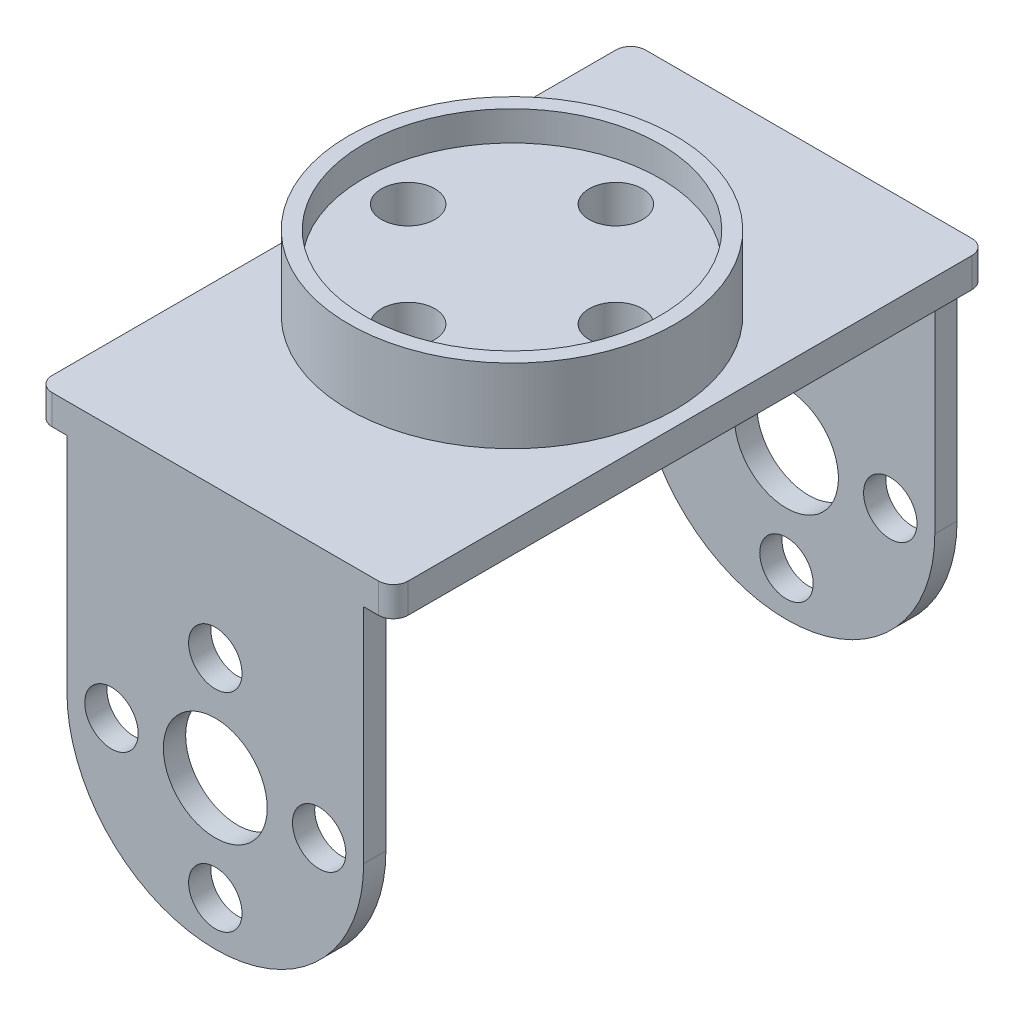
SolidWorks part; units mm, degrees
ref_plane "前视基准面" through (0, 0, 0) normal (0, 0, 1) x (1, 0, 0)
ref_plane "上视基准面" through (0, 0, 0) normal (0, 1, 0) x (1, 0, 0)
ref_plane "右视基准面" through (0, 0, 0) normal (1, 0, 0) x (0, 0, -1)
other "Configuration Table"
sketch "草图1" plane through (0, 0, 0) normal (0, 0, 1) x (1, 0, 0)
  line L1 (0, 0) -> (-24, 0)
  line L2 (0, 0) -> (0, 30)
  line L3 (0, 30) -> (-24, 30)
  line L4 (-24, 0) -> (-24, 30)
  dimension "D1" = 30
  dimension "D2" = 24
extrude "凸台-拉伸1" add sketch "草图1" along normal blind 40
sketch "草图2" plane through (0, 0, 0) normal (0, 0, -1) x (-1, 0, 0)
  line L0 (12, 0) -> (12, 50000) construction
  line L1 (24, 0) -> (0, 0) construction
  line L2 (0, 30) -> (24, 30) construction
  line L3 (2, 13) -> (2, 28)
  line L4 (2, 28) -> (0, 28)
  line L5 (0, 0) -> (0, 30) construction
  line L6 (24, 30) -> (24, 28)
  line L7 (22, 28) -> (24, 28)
  line L8 (22, 13) -> (22, 28)
  line L10 (0, 30) -> (0, 0)
  line L11 (0, 0) -> (24, 0)
  line L12 (24, 0) -> (24, 30)
  line L13 (24, 30) -> (0, 30)
  line L14 (0, 30) -> (0, 28)
  line L17 (24, 30) -> (0, 30)
  circle A0 centre (12, 13) radius 10
  point P4 (12, 0)
  line M13 (0, 30) -> (0, 0)
  line M14 (0, 0) -> (24, 0)
  line M15 (24, 0) -> (24, 30)
  dimension "D1" = 20
  dimension "D2" = 17
  dimension "D3" = 0
  dimension "D4" = 2
extrude "切除-拉伸1" cut sketch "草图2" against normal through all contours L0 A0 L3 L4 M14 M13 | L0 L7 L8 A0 M14 M15 region at (-6, 0.3046, 0) region at (-12.3046, 1.5, 0)
ref_plane "基准面1" through (0, 0, 20) normal (0, 0, -1) x (-1, 0, 0)
sketch "草图3" plane through (0, 0, 20) normal (0, 0, -1) x (-1, 0, 0)
  line L0 (2, 28) -> (22, 28)
  line L7 (0, 30) -> (0, 28)
  line L8 (0, 28) -> (2, 28)
  line L9 (2, 28) -> (2, 13)
  line L10 (22, 13) -> (22, 28)
  line L11 (22, 28) -> (24, 28)
  line L12 (24, 28) -> (24, 30)
  line L13 (24, 30) -> (0, 30)
  line L14 (0, 30) -> (0, 28)
  line L15 (0, 28) -> (2, 28)
  line L16 (2, 28) -> (2, 13)
  line L17 (22, 13) -> (22, 28)
  line L18 (22, 28) -> (24, 28)
  line L19 (24, 28) -> (24, 30)
  line L20 (24, 30) -> (0, 30)
  arc A1 (2, 13) -> (22, 13) centre (12, 13) ccw
  arc A2 (2, 13) -> (22, 13) centre (12, 13) ccw
  dimension "D1" = 0
extrude "切除-拉伸2" cut sketch "草图3" against normal blind 18.5 and the other way blind 18.5 contours L16 A2 L17 L0 region at (-12, 16.464, 20)
sketch "草图4" plane through (0, 0, 0) normal (0, 0, -1) x (-1, 0, 0)
  circle A0 centre (12, 13) radius 7 construction
  circle A1 centre (12, 6) radius 1.8
  circle A5 centre (12, 13) radius 3.5
  circle A6 centre (12, 20) radius 1.8
  circle A7 centre (19, 13) radius 1.8
  circle A8 centre (5, 13) radius 1.8
  point P14 (11.0448, 11.9373)
  dimension "D1" = 14
  dimension "D2" = 3.6
  dimension "D4" = 7
  dimension "D3" = 3.6
  dimension "D5" = 3.6
  dimension "D6" = 3.6
extrude "切除-拉伸3" cut sketch "草图4" against normal up to surface (40 mm away) up to face at (-12, 23.5, 40)
sketch "草图5" plane through (0, 30, 0) normal (0, 1, 0) x (1, 0, 0)
  line L0 (-24, -20) -> (49976, -20) construction
  line L1 (-24, -40) -> (-24, 0) construction
  line L2 (-12, 0) -> (-12, -50000) construction
  line L3 (0, 0) -> (-24, 0) construction
  circle A0 centre (-12, -20) radius 10
  circle A1 centre (-12, -20) radius 11
  point P4 (-24, -20)
  point P9 (-12, 0)
  dimension "D1" = 20
  dimension "D2" = 22
extrude "凸台-拉伸2" add sketch "草图5" along normal blind 5 separate body contours A1 A0 | A1 region at (-22.6889, 30, 20)
sketch "草图6" plane through (0, 35, 0) normal (0, 1, 0) x (1, 0, 0)
  circle A0 centre (-12, -20) radius 10
  dimension "D1" = 20
extrude "切除-拉伸4" cut sketch "草图6" against normal blind 2
sketch "草图7" plane through (0, 33, 0) normal (0, 1, 0) x (1, 0, 0)
  circle A0 centre (-12, -20) radius 7 construction
  circle A1 centre (-12, -13) radius 1.8
  circle A2 centre (-5, -20) radius 1.8
  circle A3 centre (-12, -27) radius 1.8
  circle A4 centre (-19, -20) radius 1.8
  point P14 (-12, -20)
  dimension "D1" = 14
  dimension "D2" = 3.6
  dimension "D3" = 4
extrude "切除-拉伸5" cut sketch "草图7" against normal through all
sketch "草图8" plane through (0, 28, 0) normal (0, -1, 0) x (1, 0, 0)
  circle A0 centre (-12, 27) radius 2.7
  circle A1 centre (-5, 20) radius 2.7
  circle A2 centre (-19, 20) radius 2.7
  circle A3 centre (-12, 13) radius 2.7
  dimension "D1" = 5.4
  dimension "D2" = 5.4
  dimension "D3" = 5.4
  dimension "D4" = 5.4
extrude "切除-拉伸6" cut sketch "草图8" against normal blind 2
fillet "圆角1" radius 1 4 edges at (-24, 29, 40) (0, 29, 40) (0, 29, 0) (-24, 29, 0)
